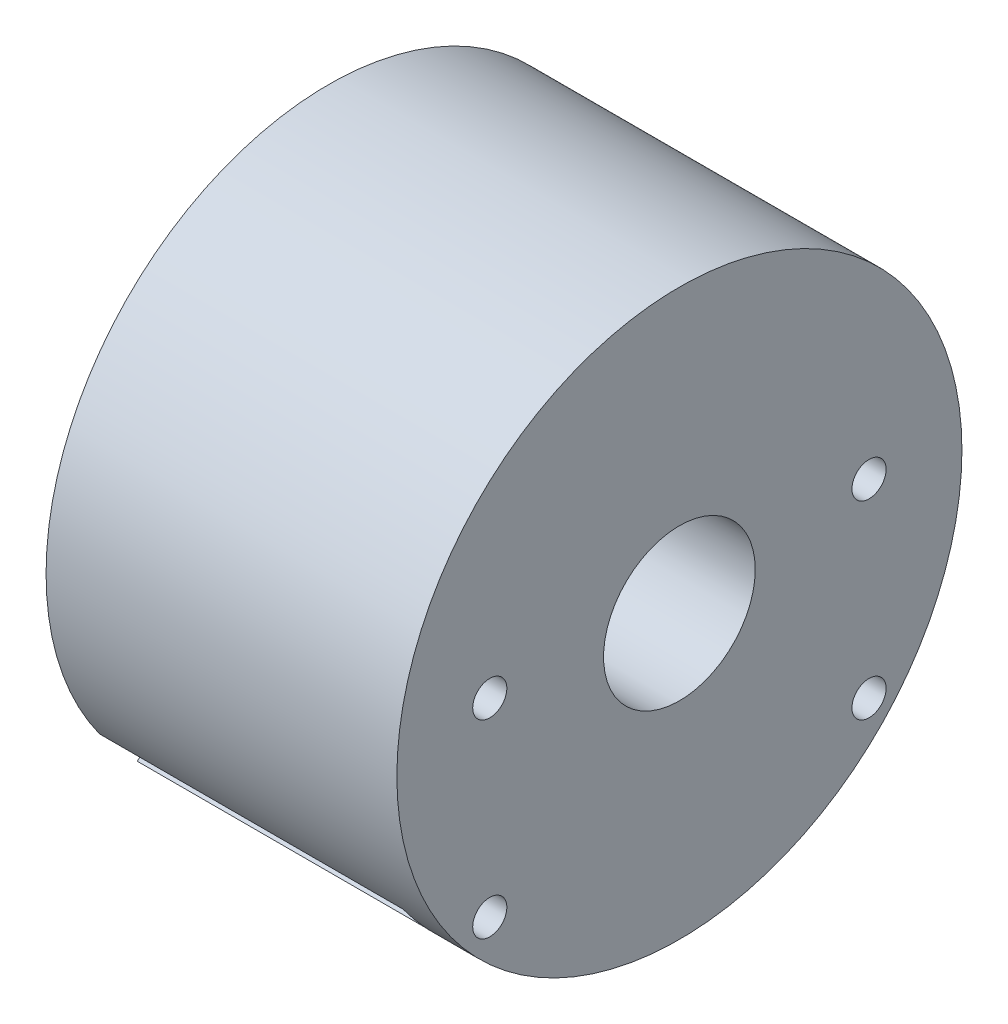
SolidWorks part; units mm, degrees
note: The reader was unsure of these and kept them because the rebuilt part matched: shared geometry of "Sketch2<3>".
material "5052-H32"
ref_plane "Front Plane" through (0, 0, 0) normal (0, 0, 1) x (1, 0, 0)
ref_plane "Top Plane" through (0, 0, 0) normal (0, 1, 0) x (1, 0, 0)
ref_plane "Right Plane" through (0, 0, 0) normal (1, 0, 0) x (0, 0, -1)
sketch "Sketch2" plane through (0, 0, 0) normal (1, 0, 0) x (0, 0, -1)
  line L0 (-21.9914, -15.5062) -> (-24.1663, -17.4365)
  line L1 (-18.0086, -19.9938) -> (-20.1836, -21.924)
  line L2 (18.0086, -19.9938) -> (20.1836, -21.924)
  line L3 (21.9914, -15.5062) -> (24.1663, -17.4365)
  line L4 (-21.9914, -15.5062) -> (-18.0086, -19.9938) construction
  line L5 (21.9914, -15.5062) -> (18.0086, -19.9938) construction
  line L6 (20, -17.75) -> (0, 0) construction
  line L7 (0, 0) -> (-20, -17.75) construction
  circle A0 centre (0, 0) radius 8 construction
  circle A1 centre (0, 0) radius 29.8 construction
  circle A2 centre (0, 0) radius 8
  circle A3 centre (0, 0) radius 29.8
  arc A4 (-18.0086, -19.9938) -> (-21.9914, -15.5062) centre (-20, -17.75) ccw
  circle A5 centre (-20, 2.25) radius 3
  circle A6 centre (20, 2.25) radius 3
  arc A7 (21.9914, -15.5062) -> (18.0086, -19.9938) centre (20, -17.75) ccw
  dimension "D1" = 6
extrude "Boss-Extrude1" add sketch "Sketch2" against normal up to vertex (37 mm away) contours A7 L3 A3 L0 A4 L1 L2 A6 A5 A2 | A6 | A5 | L3 A7 L2 A3 | L1 A4 L0 A3
hole_wizard "M4 Clearance Hole1" positions "Sketch3" profile "Sketch5" hole size "M3" standard "ISO" end condition through all
sketch "Sketch3" plane through (-37, 0, 0) normal (-1, 0, 0) x (0, 0, 1)
  point P0 (-20, 2.25)
  point P3 (20, 2.25)
  point P6 (20, -17.75)
  point P9 (-20, -17.75)
sketch "Sketch5" plane through (-37, 2.25, -20) normal (0, 1, 0) x (0, 0, 1)
  line L0 (0, 0) -> (0, 37)
  line L1 (0, 37) -> (1.8, 37)
  line L2 (1.8, 37) -> (1.8, 0)
  line L5 (1.8, 0) -> (0, 0)
  line L11 (0, -6.35) -> (0, 107.95) construction
  dimension "Thru Hole Dia." = 3.6
  dimension "Thru Hole Depth" = 37
extrude "Cut-Extrude1" cut sketch "Sketch2<3>" along normal up to vertex from vertex contours A6 | A5 | L1 A4 L0 A3 | L3 A7 L2 A3
sketch "Sketch2<3>" plane through (0, 0, 0) normal (1, 0, 0) x (0, 0, -1) same geometry as "Sketch2"
